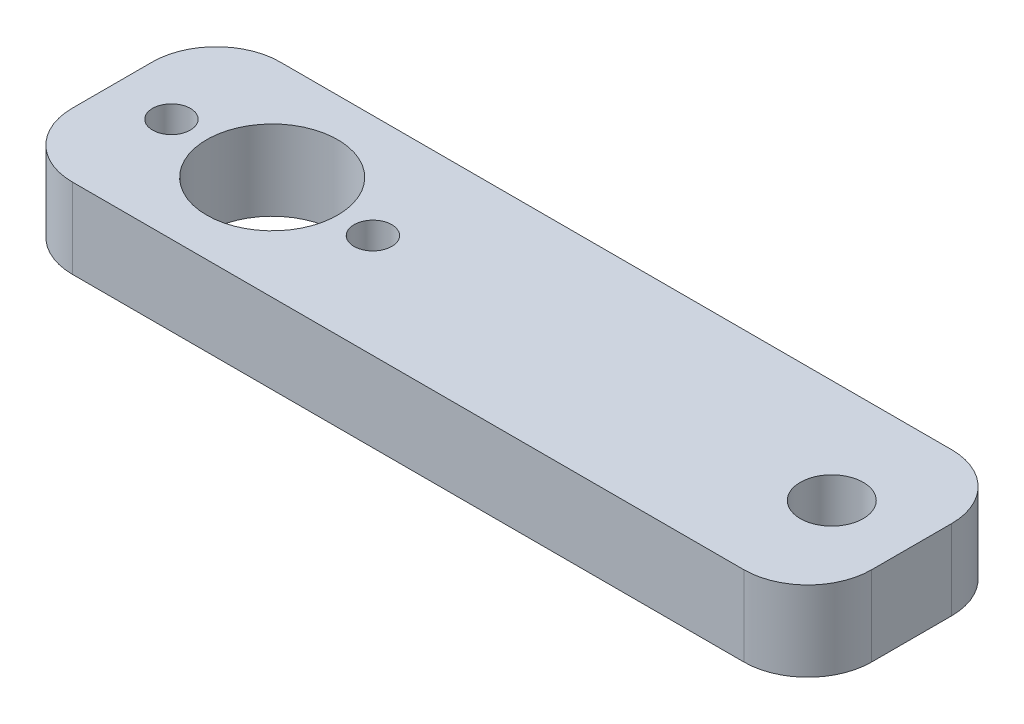
SolidWorks part; units mm, degrees
ref_plane "Front Plane" through (0, 0, 0) normal (0, 0, 1) x (1, 0, 0)
ref_plane "Top Plane" through (0, 0, 0) normal (0, 1, 0) x (1, 0, 0)
ref_plane "Right Plane" through (0, 0, 0) normal (1, 0, 0) x (0, 0, -1)
sketch "Sketch1" plane through (0, 0, 0) normal (0, 1, 0) x (1, 0, 0)
  line L1 (0, 0) -> (63.5, 0)
  line L2 (0, 0) -> (0, 16.51)
  line L3 (0, 16.51) -> (63.5, 16.51)
  line L4 (63.5, 0) -> (63.5, 16.51)
  dimension "D1" = 16.51
  dimension "D2" = 63.5
extrude "Boss-Extrude1" add sketch "Sketch1" along normal blind 6.35
hole_wizard "Ø5.0mm Dowel Hole1" positions "Sketch2" profile "Sketch3" hole size "Ø5.0" standard "ANSI Metric" end condition through all
sketch "Sketch2" plane through (0, 6.35, 0) normal (0, 1, 0) x (1, 0, 0)
  line L1 (63.5, 0) -> (63.5, 16.51) construction
  point P2 (57.15, 8.255)
  point P17 (63.5, 8.255)
  dimension "D1" = 6.35
sketch "Sketch3" plane through (57.15, 6.35, -8.255) normal (1, 0, 0) x (0, 0, 1)
  line L0 (0, 0) -> (0, 6.35)
  line L1 (0, 6.35) -> (2.5, 6.35)
  line L2 (2.5, 6.35) -> (2.5, 0)
  line L5 (2.5, 0) -> (0, 0)
  line L11 (0, -6.35) -> (0, 107.95) construction
  dimension "Thru Hole Dia." = 5
  dimension "Thru Hole Depth" = 6.35
hole_wizard "Ø10.0mm Dowel Hole1" positions "3DSketch1" profile "Sketch4" hole size "Ø10.0" standard "ANSI Metric" end condition through all
sketch3d "3DSketch1"
  line L0 (0, 6.35, -16.51) -> (0, 6.35, 0) construction
  line L1 (0, 6.35, -8.255) -> (63.5, 6.35, -8.255) construction
  line L2 (63.5, 6.35, 0) -> (63.5, 6.35, -16.51) construction
  point P0 (12.7, 6.35, -8.255)
  dimension "D1" = 12.7
sketch "Sketch4" plane through (12.7, 6.35, -8.255) normal (1, 0, 0) x (0, 0, 1)
  line L0 (0, 0) -> (0, 6.35)
  line L1 (0, 6.35) -> (5.2, 6.35)
  line L2 (5.2, 6.35) -> (5.2, 0)
  line L5 (5.2, 0) -> (0, 0)
  line L11 (0, -6.35) -> (0, 107.95) construction
  dimension "Thru Hole Dia." = 10.4
  dimension "Thru Hole Depth" = 6.35
hole_wizard "Ø3.0mm Dowel Hole1" positions "Sketch5" profile "Sketch6" hole size "Ø3.0" standard "ANSI Metric" end condition through all
sketch "Sketch5" plane through (0, 6.35, 0) normal (0, 1, 0) x (1, 0, 0)
  line L0 (0, 16.51) -> (0, 0) construction
  point P0 (4.699, 8.255)
  point P2 (20.701, 8.255)
  point P7 (0, 8.255)
sketch "Sketch6" plane through (4.699, 6.35, -8.255) normal (1, 0, 0) x (0, 0, 1)
  line L0 (0, 0) -> (0, 6.35)
  line L1 (0, 6.35) -> (1.5, 6.35)
  line L2 (1.5, 6.35) -> (1.5, 0)
  line L5 (1.5, 0) -> (0, 0)
  line L11 (0, -6.35) -> (0, 107.95) construction
  dimension "Thru Hole Dia." = 3
  dimension "Thru Hole Depth" = 6.35
fillet "Fillet1" radius 5.08 4 edges at (63.5, 3.175, -16.51) (63.5, 3.175, 0) (0, 3.175, 0) (0, 3.175, -16.51)
